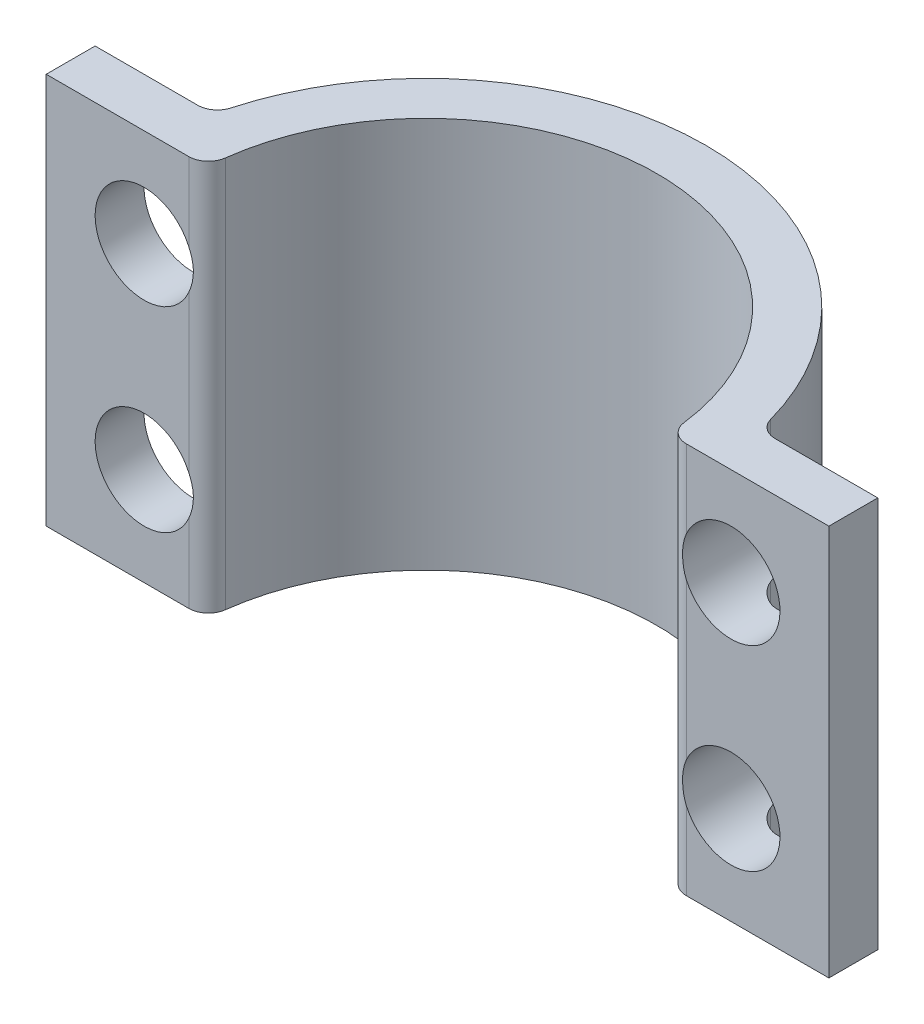
SolidWorks part; units mm, degrees
ref_plane "Front Plane" through (0, 0, 0) normal (0, 0, 1) x (1, 0, 0)
ref_plane "Top Plane" through (0, 0, 0) normal (0, 1, 0) x (1, 0, 0)
ref_plane "Right Plane" through (0, 0, 0) normal (1, 0, 0) x (0, 0, -1)
sketch "Sketch2" plane through (0, 0, 0) normal (0, 1, 0) x (1, 0, 0)
  line L0 (0, 0) -> (-10.4194, 0)
  line L1 (-10.4194, 0) -> (-10.4194, 3.175)
  line L2 (-10.4194, 3.175) -> (-2.7628, 3.175)
  line L3 (32.7241, 3.175) -> (40.3806, 3.175)
  line L4 (40.3806, 3.175) -> (40.3806, 0)
  line L5 (40.3806, 0) -> (29.9613, 0)
  line L6 (14.9806, 0.1727) -> (14.9806, 50000.1727) construction
  circle A0 centre (14.9806, -0.762) radius 15 construction
  arc A1 (29.9613, 0) -> (0, 0) centre (14.9806, -0.762) ccw
  arc A2 (32.7241, 3.175) -> (-2.7628, 3.175) centre (14.9806, -0.762) ccw
  point P5 (-4.0694, 0)
  point P8 (34.0306, 0)
  dimension "D1" = 15
  dimension "D2" = 3.175
  dimension "D3" = 38.1
  dimension "D4" = 3.175
  dimension "D5" = 6.35
  dimension "D6" = 0.762
extrude "Boss-Extrude1" add sketch "Sketch2" against normal blind 25.4
sketch "Sketch3" plane through (0, 0, 0) normal (0, 0, 1) x (1, 0, 0)
  line L0 (14.9806, 0) -> (14.9806, -50000) construction
  line L1 (29.9613, 0) -> (0, 0) construction
  line L2 (-10.4194, 0) -> (0, 0) construction
  circle A0 centre (-4.0694, -6.35) radius 3.175
  circle A1 centre (34.0306, -6.35) radius 3.175
  circle A2 centre (-4.0694, -19.05) radius 3.175
  circle A3 centre (34.0306, -19.05) radius 3.175
  point P8 (14.9806, 0)
  dimension "D1" = 6.35
  dimension "D4" = 12.7
  dimension "D2" = 38.1
  dimension "D3" = 6.35
extrude "Cut-Extrude1" cut sketch "Sketch3" against normal through all
fillet "Fillet1" radius 1.27 8 edges at (32.7241, -23.6719, -3.175) (32.7241, -12.7, -3.175) (32.7241, -1.7281, -3.175) (-2.7628, -1.7281, -3.175) (-2.7628, -23.6719, -3.175) (-2.7628, -12.7, -3.175) (29.9613, -12.7, 0) (0, -12.7, 0)
